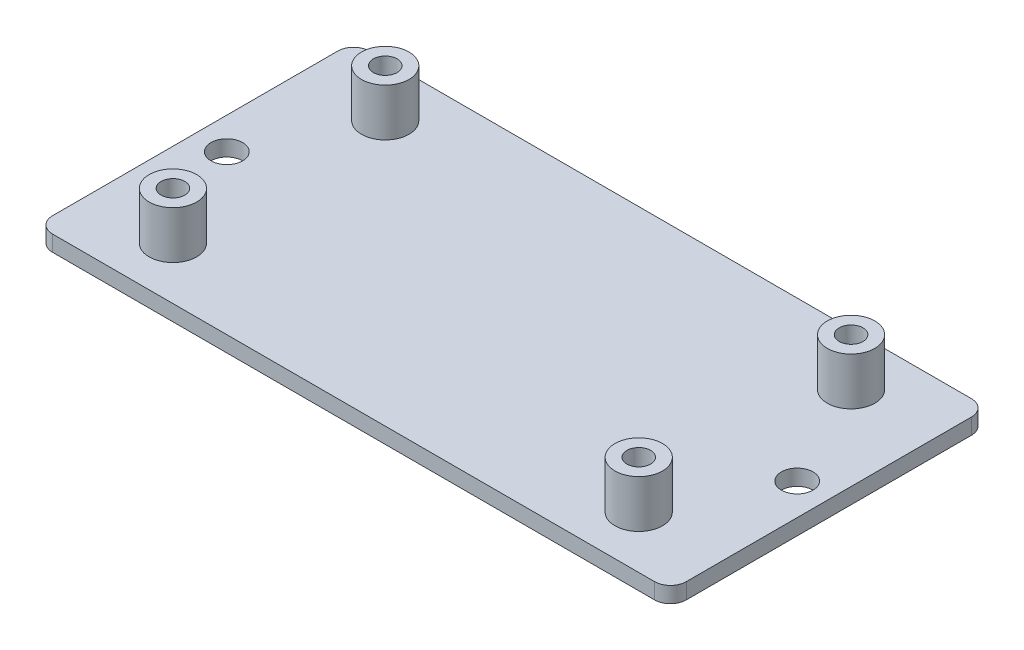
SolidWorks part; units mm, degrees
material "ABS"
ref_plane "Спереди" through (0, 0, 0) normal (0, 0, 1) x (1, 0, 0)
ref_plane "Сверху" through (0, 0, 0) normal (0, 1, 0) x (1, 0, 0)
ref_plane "Справа" through (0, 0, 0) normal (1, 0, 0) x (0, 0, -1)
sketch "Эскиз1" plane through (0, 0, 0) normal (0, 1, 0) x (1, 0, 0)
  line L1 (0, 0) -> (80, 0)
  line L2 (0, 0) -> (0, -40)
  line L3 (0, -40) -> (80, -40)
  line L4 (80, 0) -> (80, -40)
  dimension "D1" = 40
  dimension "D2" = 80
extrude "Бобышка-Вытянуть1" add sketch "Эскиз1" along normal blind 2
sketch "Эскиз2" plane through (0, 2, 0) normal (0, 1, 0) x (1, 0, 0)
  line L0 (0, 0) -> (0, -40) construction
  line L1 (80, 0) -> (0, 0) construction
  line L2 (0, -40) -> (80, -40) construction
  line L3 (80, -40) -> (80, 0) construction
  circle A0 centre (10.6, -6.6) radius 3
  circle A1 centre (10.6, -33.4) radius 3
  circle A2 centre (69.4, -6.6) radius 3
  circle A3 centre (69.4, -33.4) radius 3
  dimension "D1" = 10.6
  dimension "D2" = 6.6
  dimension "D3" = 10.6
  dimension "D4" = 6.6
  dimension "D5" = 6.6
  dimension "D6" = 10.6
  dimension "D7" = 10.6
  dimension "D8" = 6.6
  dimension "D9" = 6
  dimension "D10" = 6
  dimension "D11" = 6
  dimension "D12" = 6
extrude "Бобышка-Вытянуть2" add sketch "Эскиз2" along normal blind 6
sketch "Эскиз3" plane through (0, 8, 0) normal (0, 1, 0) x (1, 0, 0)
  circle A0 centre (10.6, -6.6) radius 1.5
  circle A1 centre (10.6, -33.4) radius 1.5
  circle A2 centre (69.4, -6.6) radius 1.5
  circle A3 centre (69.4, -33.4) radius 1.5
  dimension "D1" = 3
  dimension "D2" = 3
  dimension "D3" = 3
  dimension "D4" = 3
extrude "Вырез-Вытянуть1" cut sketch "Эскиз3" against normal through all both and the other way through all
sketch "Эскиз4" plane through (0, 2, 0) normal (0, 1, 0) x (1, 0, 0)
  line L0 (0, -20) -> (80, -20) construction
  line L1 (0, 0) -> (0, -40) construction
  line L2 (80, -40) -> (80, 0) construction
  circle A0 centre (4, -20) radius 2
  circle A1 centre (76, -20) radius 2
  dimension "D1" = 4
  dimension "D2" = 4
  dimension "D3" = 4
  dimension "D4" = 4
extrude "Вырез-Вытянуть2" cut sketch "Эскиз4" against normal through all both and the other way through all
fillet "Скругление1" radius 2 1 edges at (0, 1, 0) type face fillet first side face at (40, 1, 0) second side face at (0, 1, 20)
fillet "Скругление2" radius 2 1 edges at (0, 1, 40) type face fillet first side face at (0, 1, 21) second side face at (40, 1, 40)
fillet "Скругление3" radius 2 1 edges at (80, 1, 40) type face fillet first side face at (41, 1, 40) second side face at (80, 1, 20)
fillet "Скругление4" radius 2 1 edges at (80, 1, 0) type face fillet first side face at (41, 1, 0) second side face at (80, 1, 19)
